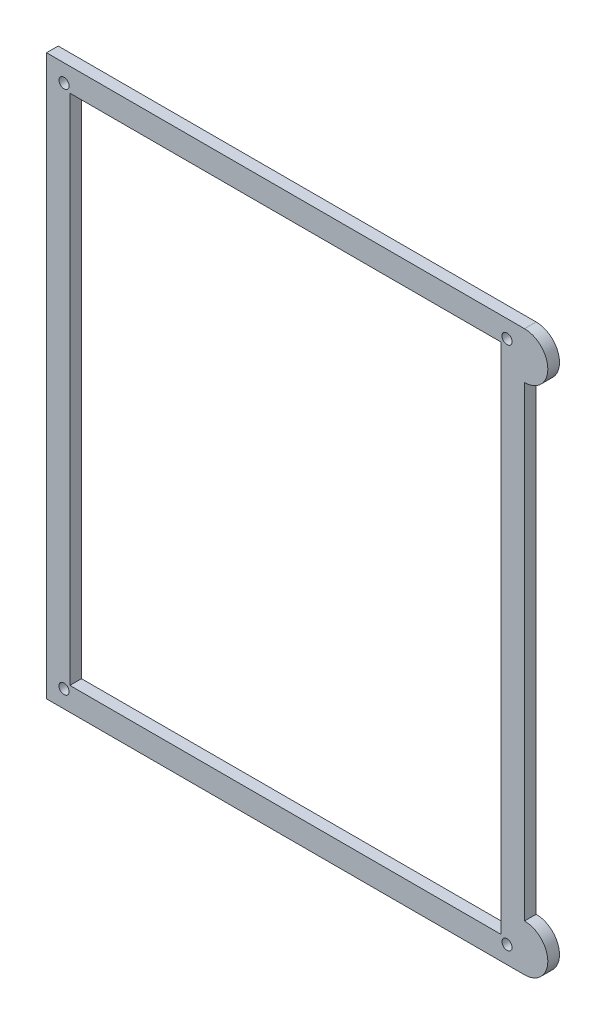
SolidWorks part; units mm, degrees
ref_plane "Front Plane" through (0, 0, 0) normal (0, 0, 1) x (1, 0, 0)
ref_plane "Top Plane" through (0, 0, 0) normal (0, 1, 0) x (1, 0, 0)
ref_plane "Right Plane" through (0, 0, 0) normal (1, 0, 0) x (0, 0, -1)
sketch "Sketch1" plane through (0, 0, 0) normal (0, 0, 1) x (1, 0, 0)
  line L0 (254, 6.35) -> (254, -273.05) construction
  line L1 (-19.05, -285.75) -> (241.3, -285.75)
  line L2 (-19.05, -285.75) -> (-19.05, 19.05)
  line L3 (-19.05, 19.05) -> (241.3, 19.05)
  line L4 (241.3, -285.75) -> (241.3, 19.05)
  line L5 (-19.05, -285.75) -> (241.3, 19.05) construction
  line L6 (-19.05, 19.05) -> (241.3, -285.75) construction
  line L7 (-6.35, 6.35) -> (228.6, 6.35)
  line L8 (-6.35, 6.35) -> (-6.35, -273.05)
  line L9 (-6.35, -273.05) -> (228.6, -273.05)
  line L10 (228.6, 6.35) -> (228.6, -273.05)
  line L11 (-6.35, 6.35) -> (228.6, -273.05) construction
  line L12 (-6.35, -273.05) -> (228.6, 6.35) construction
  circle A0 centre (-9.525, -276.225) radius 2.75
  circle A1 centre (231.775, -276.225) radius 2.75
  circle A2 centre (231.775, 9.525) radius 2.75
  circle A3 centre (-9.525, 9.525) radius 2.75
  circle A4 centre (231.775, 9.525) radius 2.75 construction
  arc A5 (241.3, 19.05) -> (241.3, -6.35) centre (241.3, 6.35) cw
  arc A6 (241.3, -260.35) -> (241.3, -285.75) centre (241.3, -273.05) cw
  point P4 (111.125, -133.35)
  point P24 (111.125, -133.35)
  point P25 (0, 0)
  point P30 (0, 0)
  point P31 (0, 0)
  point P32 (0, 0)
  point P33 (-9.525, -276.225)
  dimension "D1" = 12.7
  dimension "D2" = 12.7
  dimension "D3" = 12.7
extrude "Boss-Extrude1" add sketch "Sketch1" along normal blind 6.35 contours L1 L4 L3 L2 A3 A2 A1 A0 L7 L10 L9 L8 | A6 L4 | A5 L4 region at (-15.0414, -133.35, 0) region at (246.69, -273.05, 0) region at (246.69, 6.35, 0)
